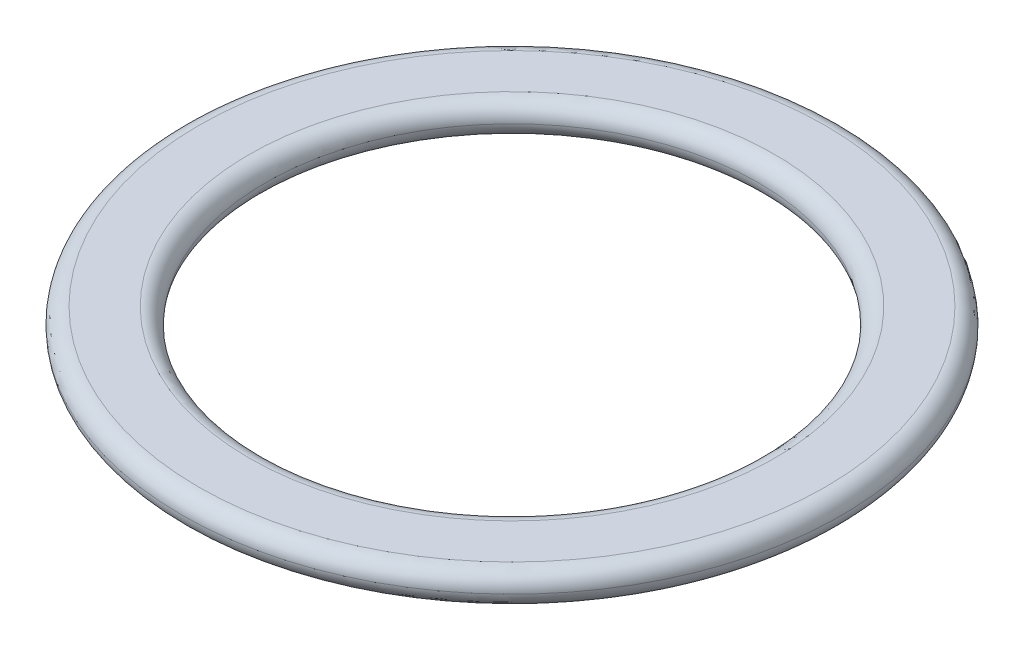
SolidWorks part; units mm, degrees
material "HYPALON"
ref_plane "Ön Düzlem" through (0, 0, 0) normal (0, 0, 1) x (1, 0, 0)
ref_plane "Üst Düzlem" through (0, 0, 0) normal (0, 1, 0) x (1, 0, 0)
ref_plane "Sağ Düzlem" through (0, 0, 0) normal (1, 0, 0) x (0, 0, -1)
sketch "Çizim1" plane through (0, 0, 0) normal (0, 1, 0) x (1, 0, 0)
  circle A0 centre (0, 0) radius 12.31
extrude "Yükseklik-Ekstrüzyon1" add sketch "Çizim1" along normal blind 1.21
fillet "Radyus1" radius 0.61 1 edges at (0, 1.21, 12.31)
fillet "Radyus2" radius 0.61 1 edges at (0, 0, 12.31)
sketch "Çizim2" plane through (0, 1.21, 0) normal (0, 1, 0) x (1, 0, 0)
  circle A0 centre (0, 0) radius 9.21
extrude "Kes-Ekstrüzyon1" cut sketch "Çizim2" along normal blind 1.21 and the other way blind 11
fillet "Radyus3" radius 0.61 1 edges at (0, 1.21, 9.21)
fillet "Radyus4" radius 0.61 1 edges at (0, 0, 9.21)
